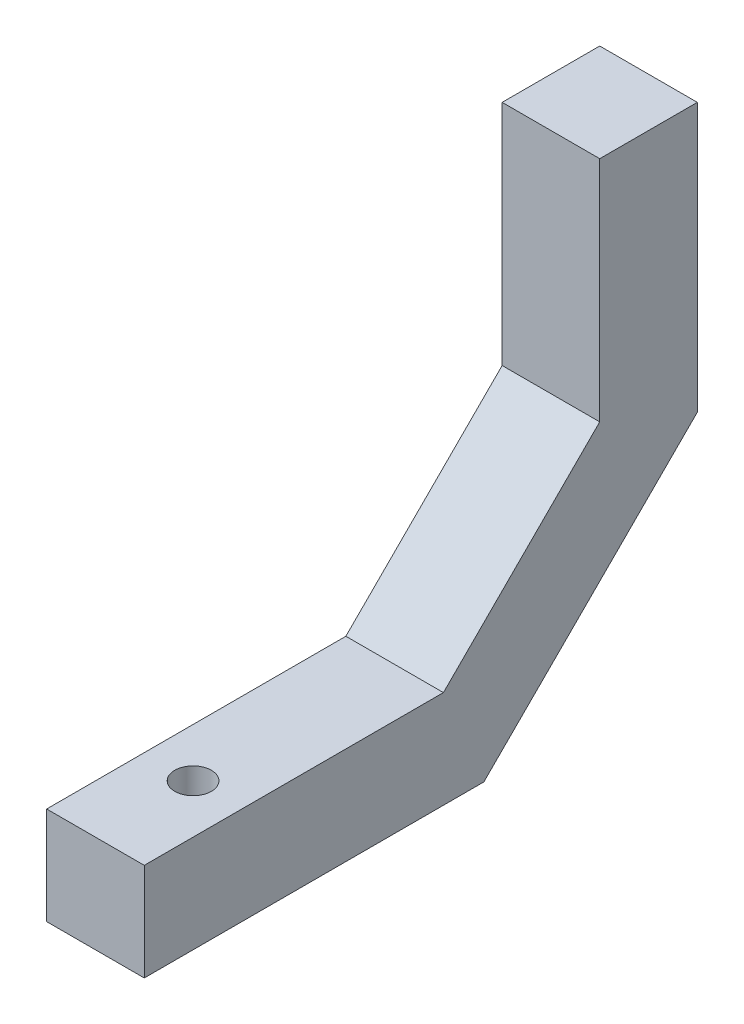
SolidWorks part; units mm, degrees
ref_plane "Front Plane" through (0, 0, 0) normal (0, 0, 1) x (1, 0, 0)
ref_plane "Top Plane" through (0, 0, 0) normal (0, 1, 0) x (1, 0, 0)
ref_plane "Right Plane" through (0, 0, 0) normal (1, 0, 0) x (0, 0, -1)
ref_axis "Z" through (0, 0, 46.725) along (0, 0, -1)
sketch "Sketch1" plane through (0, 0, 0) normal (1, 0, 0) x (0, 0, -1)
  line L0 (-8, 4) -> (0, 4)
  line L1 (0, 4) -> (0, -18)
  line L2 (0, -18) -> (-17.5, -35.5)
  line L3 (-17.5, -35.5) -> (-37.34, -35.5)
  line L4 (-37.34, -35.5) -> (-37.34, -27.5) construction
  line L5 (-37.34, -27.5) -> (-20.8137, -27.5)
  line L6 (-20.8137, -27.5) -> (-8, -14.6863)
  line L7 (-8, -14.6863) -> (-8, 4)
  line L8 (-13.4134, -20.0997) -> (-7.7566, -25.7566) construction
  line L10 (-37.34, -27.5) -> (-45.34, -27.5)
  line L11 (-37.34, -27.5) -> (-37.34, -35.5) construction
  line L12 (-37.34, -35.5) -> (-45.34, -35.5)
  line L13 (-45.34, -27.5) -> (-45.34, -35.5)
  dimension "D1" = 8
  dimension "D2" = 37.34
  dimension "D3" = 35.5
  dimension "D4" = 4
  dimension "D5" = 135
  dimension "D6" = 17.5
  dimension "D7" = 8
extrude "Boss-Extrude1" add sketch "Sketch1" along normal blind 4 and the other way blind 4
sketch "Sketch3" plane through (0, -27.5, 0) normal (0, 1, 0) x (1, 0, 0)
  line L0 (-4.4, 0) -> (4.4, 0) construction
  line L1 (0, -21.725) -> (0, 21.725) construction
  circle A0 centre (0, -37.34) radius 1.5
  dimension "D2" = 3
  dimension "D1" = 37.34
extrude "Cut-Extrude1" cut sketch "Sketch3" against normal through all
ref_axis "Axis1" through (0, -27.5, 37.34) along (0, 1, 0)
equation "\"rbracket-width\"= 8"
equation "\"D1@Boss-Extrude1\"=\"rbracket-width\"/2"
equation "\"D2@Boss-Extrude1\"=\"rbracket-width\"/2"
equation "\"EyeCaptureRadius\"= ( \"EyeDiameter\" + \"EyeClearance\" ) / 2"
equation "\"rbracket_planetocenterline_dist\"= \"BasePlaneDistance\""
equation "\"D2@Sketch1\"=\"rbracket_planetocenterline_dist\""
equation "\"EyeDiameter\" = 35"
equation "\"BasePlaneDistance\" = \"EyeDiameter\"/2+19.84"
equation "\"EyeClearance\" = 2"
equation "\"D1@Sketch1\"=\"rbracket-width\""
equation "\"D3@Sketch1\"=(\"EyeDiameter\"+\"EyeClearance\"+\"EyeClearance\")/2 + \"L2Thickness\" + \"rbracket-width\""
equation "\"D4@Sketch1\"=\"rbracket-width\"/2"
equation "\"D6@Sketch1\"=\"EyeDiameter\"/2"
equation "\"D7@Sketch1\"=\"rbracket-width\""
equation "\"D1@Sketch3\"=\"BasePlaneDistance\""
equation "\"L2Thickness\" = 8"
